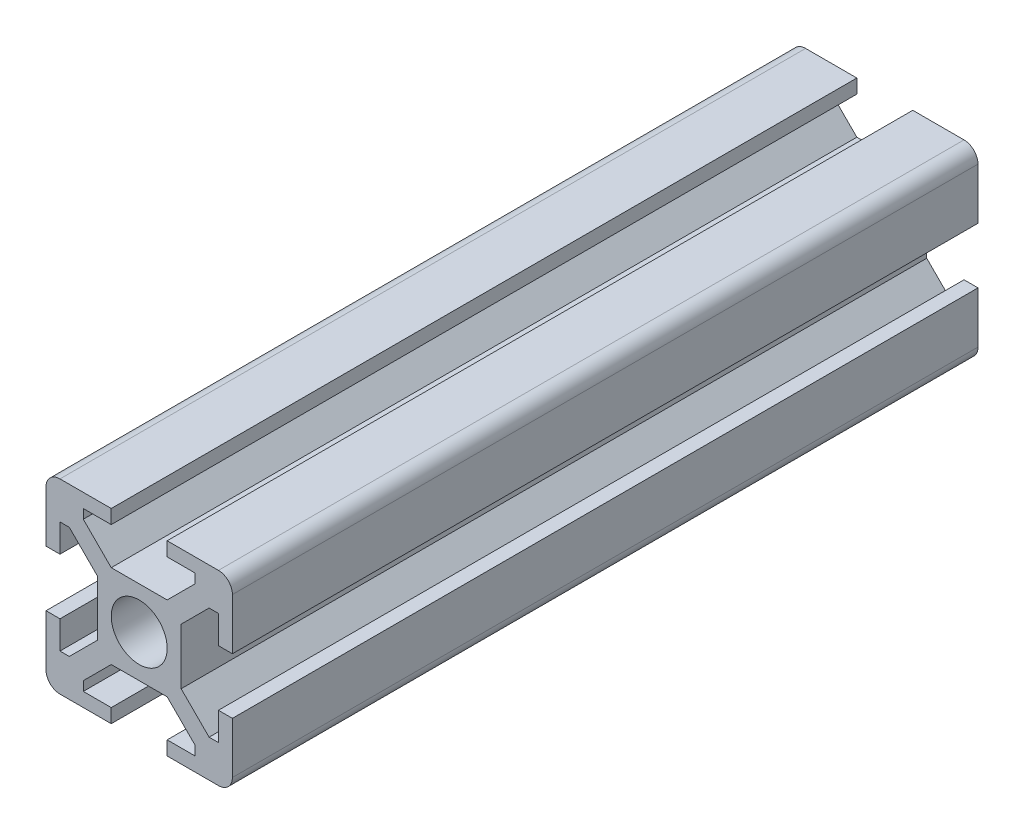
SolidWorks part; units mm, degrees
ref_plane "Plan de face" through (0, 0, 0) normal (0, 0, 1) x (1, 0, 0)
ref_plane "Plan de dessus" through (0, 0, 0) normal (0, 1, 0) x (1, 0, 0)
ref_plane "Plan de droite" through (0, 0, 0) normal (1, 0, 0) x (0, 0, -1)
sketch "Esquisse1" plane through (0, 0, 0) normal (0, 0, 1) x (1, 0, 0)
  line L0 (-10, 10) -> (10, -10) construction
  line L1 (-10, 10) -> (10, 10)
  line L2 (-10, 10) -> (-10, -10)
  line L3 (-10, -10) -> (10, -10)
  line L4 (10, 10) -> (10, -10)
  dimension "D1" = 20
extrude "Extrusion1" add sketch "Esquisse1" along normal mid plane 80
fillet "Congé1" radius 1.5 4 edges at (-10, -10, 0) (10, -10, 0) (-10, 10, 0) (10, 10, 0)
sketch "Esquisse2" plane through (0, 0, -40) normal (0, 0, -1) x (-1, 0, 0)
  line L0 (-10, 3) -> (-10, -3)
  line L1 (-10, -8.5) -> (-10, 8.5) construction
  line L2 (-10, -3) -> (-8.5, -3)
  line L3 (-8.5, -3) -> (-8.5, -6)
  line L4 (-8.5, 6) -> (-7.5, 6)
  line L5 (-4.5, -3) -> (-4.5, 3)
  line L6 (-7.5, 6) -> (-4.5, 3)
  line L7 (-8.5, 6) -> (-8.5, 3)
  line L8 (-8.5, 3) -> (-10, 3)
  line L9 (0, 0) -> (-10, 0) construction
  line L10 (-8.5, -6) -> (-7.5, -6)
  line L11 (-7.5, -6) -> (-4.5, -3)
  point P4 (-10, 0)
  dimension "D1" = 6
  dimension "D2" = 12
  dimension "D3" = 1.5
  dimension "D4" = 5.5
  dimension "D5" = 135
extrude "Enlèv. mat.-Extru.1" cut sketch "Esquisse2" against normal through all
ref_axis "Axe1" through (0, 0, 9.3338) along (0, 0, -1)
pattern_circular "Répétition circulaire1" count 4 over 360 about axis through (0, 0, 9.3338) along (0, 0, -1) of "Enlèv. mat.-Extru.1"
hole_wizard "Trou taraudé M6x1.01" positions "Esquisse4" profile "Esquisse5" tap size "M6x1.0" standard "Ansi Métrique"
sketch "Esquisse4" plane through (0, 0, -40) normal (0, 0, -1) x (-1, 0, 0)
  point P0 (0, 0)
sketch "Esquisse5" plane through (0, 0, -40) normal (1, 0, 0) x (0, 1, 0)
  line L0 (0, 0) -> (0, 31.5022)
  line L1 (0, 31.5022) -> (2.5, 30)
  line L2 (2.5, 30) -> (2.5, 24)
  line L3 (2.5, 24) -> (3, 24)
  line L4 (3, 24) -> (3, 0)
  line L5 (3, 0) -> (0, 0)
  line L10 (0, 31.5022) -> (-2.5, 30) construction
  line L11 (0, -6.35) -> (0, 107.95) construction
  dimension "Diamètre du trou pour taraudage" = 5
  dimension "Profondeur du trou pour taraudage" = 30
  dimension "Diamètre principal du filetage" = 6
  dimension "Profondeur du filetage" = 24
  dimension "Angle de pointe" = 118
mirror "Symétrie1" about plane through (0, 0, 0) normal (0, 0, 1) of "Trou taraudé M6x1.01"
